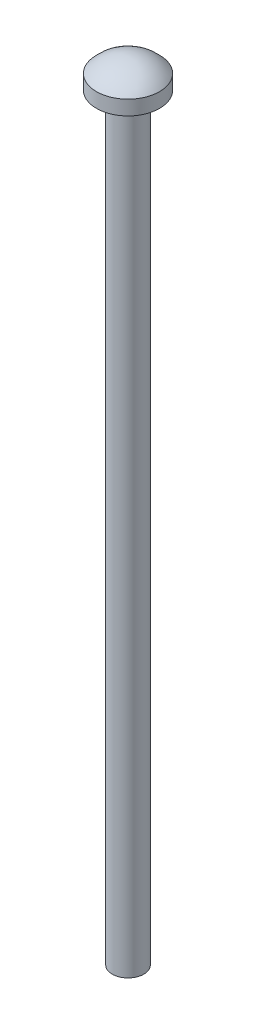
SolidWorks part; units mm, degrees
material "Plain Carbon Steel"
ref_plane "Front Plane" through (0, 0, 0) normal (0, 0, 1) x (1, 0, 0)
ref_plane "Top Plane" through (0, 0, 0) normal (0, 1, 0) x (1, 0, 0)
ref_plane "Right Plane" through (0, 0, 0) normal (1, 0, 0) x (0, 0, -1)
ref_axis "Axis1" through (0, -55, 0) along (0, 1, 0)
sketch "Sketch2" plane through (0, 0, 0) normal (0, 1, 0) x (1, 0, 0)
  line L0 (0, -20.955) -> (0, 20.955) construction
  line L1 (0, 34.925) -> (1.5875, 34.925)
  line L2 (0, 34.925) -> (0, 3.5498)
  line L3 (0, 3.5498) -> (1.5875, 3.5498) construction
  line L4 (1.5875, 34.925) -> (1.5875, 3.5498)
  line L5 (3.175, 0) -> (3.175, 3.5498) construction
  line L6 (-0.5513, 3.1268) -> (0, 0)
  circle A0 centre (0, 0) radius 3.175 construction
  circle A1 centre (0, 0) radius 1.5875 construction
  arc A2 (1.5875, 3.5498) -> (2.1167, 2.3665) centre (3.175, 3.5498) ccw
  arc A3 (0, 3.5498) -> (1.0583, 1.1833) centre (3.175, 3.5498) ccw
  arc A4 (2.1167, 2.3665) -> (-0.5513, 3.1268) centre (0, 0) cw
  circle A5 centre (0, 0) radius 1.5875 construction
  arc A6 (1.0583, 1.1833) -> (-0.2757, 1.5634) centre (0, 0) cw
  point P10 (3.175, 3.5498)
  dimension "D1" = 6.35
  dimension "D2" = 3.175
  dimension "D5" = 31.75
  dimension "D3" = 1.5875
  dimension "D4" = 10
sketch "Sketch3" plane through (0, 0, 0) normal (1, 0, 0) x (0, 0, -1)
  line L0 (0, 49.3995) -> (0, -49.3995) construction
  line L1 (0, -55) -> (0, 55) construction
  line L2 (0, -49.3995) -> (-1.5875, -49.3995)
  line L3 (-1.5875, -49.3995) -> (-1.5875, 26.8005)
  line L4 (-1.5875, 26.8005) -> (-3.175, 26.8005)
  line L5 (-3.175, 26.8005) -> (-3.175, 28.2634)
  line L6 (0, 29.7264) -> (0, 49.3995) construction
  line L7 (0, 29.7264) -> (-3.175, 29.7264) construction
  line L8 (-3.175, 29.7264) -> (-3.175, 28.2634) construction
  line L9 (0, 0) -> (0, 49.3995) construction
  line L11 (1.5634, 0) -> (-1.5875, 0) construction
  line L12 (0, -49.3995) -> (0, 29.7264)
  arc A0 (-3.175, 28.2634) -> (0, 29.7264) centre (0, 25.5496) cw
  point P12 (0, 0)
  dimension "D1" = 76.2
  dimension "D2" = 1.5875
  dimension "D3" = 3.175
revolve "Revolve3" add sketch "Sketch3" angle 360 about L12
